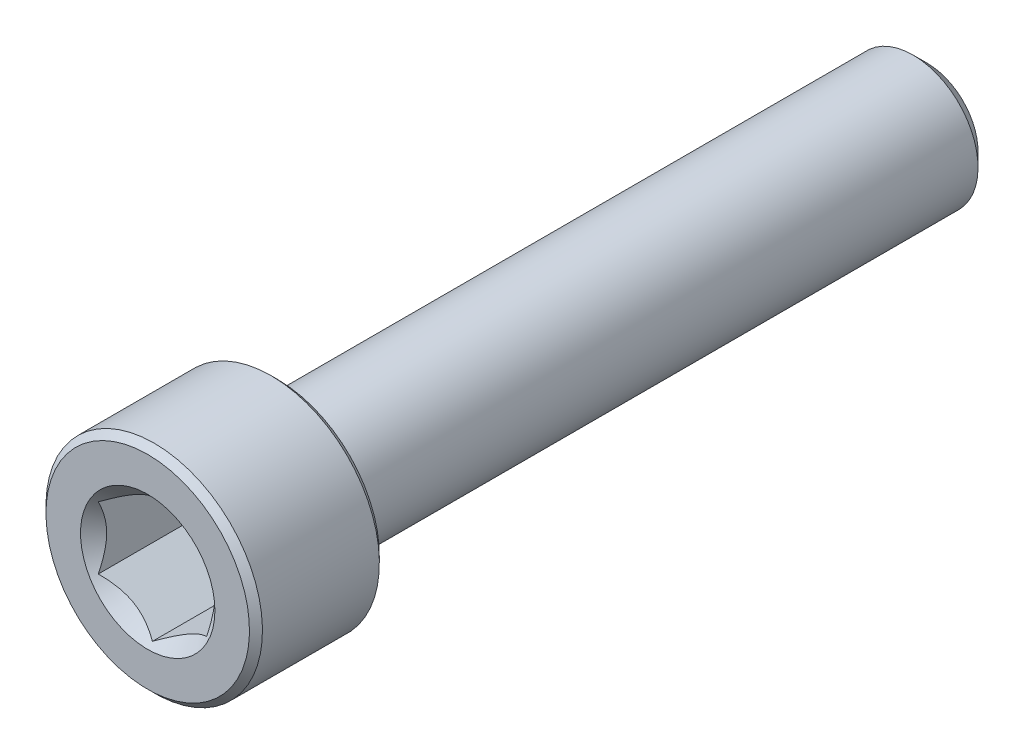
SolidWorks part; units mm, degrees
material "Alloy Steel"
ref_plane "Front Plane" through (0, 0, 0) normal (0, 0, 1) x (1, 0, 0)
ref_plane "Top Plane" through (0, 0, 0) normal (0, 1, 0) x (1, 0, 0)
ref_plane "Right Plane" through (0, 0, 0) normal (1, 0, 0) x (0, 0, -1)
sketch "Sketch1" plane through (0, 0, 0) normal (1, 0, 0) x (0, 0, -1)
  line L0 (-18, 0) -> (18, 0) construction
  line L1 (18, 0) -> (18, 2.3505) construction
  line L2 (18, 2.3505) -> (17.3505, 3) construction
  line L3 (17.3505, 3) -> (17.25, 3) construction
  line L4 (17.25, 3) -> (-12, 3) construction
  line L5 (-12, 3) -> (-12, 5) construction
  line L6 (-12, 5) -> (-18, 5) construction
  line L7 (-18, 5) -> (-18, 0) construction
  line L8 (18, 2.3505) -> (18, 3) construction
  line L9 (17.9375, 3.1083) -> (18.4375, 2.2422) construction
  line L10 (18.4375, 2.2422) -> (18.9375, 3.1083) construction
  line L11 (18.9375, 3.1083) -> (17.9375, 3.1083) construction
  line L12 (18.4375, 3.1083) -> (18.4375, 3) construction
  line L13 (18.4375, 2.2422) -> (18.4375, 2.3505) construction
  line L14 (18.375, 2.3505) -> (18.5, 2.3505) construction
  line L15 (18, 3) -> (18.875, 3) construction
  line L16 (17.9687, 3.0541) -> (18.9063, 3.0541) construction
  line L17 (18, 0) -> (18, -3) construction
  line L18 (-12.3, 5) -> (-12, 4.7) construction
  line L19 (-17.7, 5) -> (-18, 4.7) construction
  line L20 (-12, 3) -> (-12, 0) construction
  line L21 (-12, 1.5) -> (-2, 1.5) construction
  line L22 (-2, 1.5) -> (8, 1.5) construction
  line L23 (8, 1.5) -> (18, 1.5) construction
  line L24 (-2, 1.5) -> (-2, 3) construction
  line L25 (-2, 3) -> (-2, 5) construction
  line L26 (8, 1.5) -> (8, 5) construction
  point P0 (-18, 2.5)
  point P3 (15.5, 3)
  point P4 (0, 0)
  point P18 (8, 3)
  point P22 (18.4375, 2.3505)
  point P24 (17.25, 3)
  point P25 (18.4375, 3)
  point P28 (18.4375, 3.0541)
  point P29 (15.5, -3)
  point P30 (-2, 3)
  point P31 (-15, 5)
  point P37 (-13.05, 5)
  point P38 (-17.55, 5)
  point P45 (-2, 1.5)
  point P46 (8, 1.5)
  dimension "D2" = 0.125
  dimension "D7" = 0.3
  dimension "D8" = 0.3
  dimension "D9" = 0.3
  dimension "D10" = 0.15
  dimension "D11" = 0.75
  dimension "Drive Size" = 5
  dimension "Head Diameter" = 10
  dimension "Head Height" = 6
  dimension "Thread Pitch" = 1
  dimension "Thread Dia" = 6
  dimension "Length" = 30
  dimension "D12" = 0.75
  dimension "D4" = 2.5
  dimension "D3" = 45
sketch "Sketch2" plane through (0, 0, 0) normal (1, 0, 0) x (0, 0, -1)
  line L0 (-18, 0) -> (-18, 4.7)
  line L1 (-17.7, 5) -> (-12.3, 5)
  line L2 (-12, 4.7) -> (-12, 3.3)
  line L4 (17.3505, 3) -> (18, 2.3505)
  line L5 (18, 2.3505) -> (18, 0)
  line L6 (-12, 5) -> (-18, 5) construction
  line L7 (18, 0) -> (-18, 0)
  line L8 (-17.7, 5) -> (-18, 4.7) construction
  line L10 (-17.7, 5) -> (-18, 4.7)
  line L14 (-12.3, 5) -> (-12, 4.7) construction
  line L16 (-12.3, 5) -> (-12, 4.7)
  line L17 (-12, 3) -> (-12, 5) construction
  line L19 (-11.7, 3) -> (17.3505, 3)
  line L20 (17.25, 3) -> (-12, 3) construction
  arc A1 (-12, 3.3) -> (-11.7, 3) centre (-11.7, 3.3) ccw
  dimension "D3" = 0.3
revolve "Revolve1" add sketch "Sketch2" angle 360 about L7
sketch "Sketch3" plane through (0, 0, 18) normal (0, 0, 1) x (1, 0, 0)
  line L1 (2.5, -1.4434) -> (2.5, 1.4434)
  line L2 (2.5, 1.4434) -> (0, 2.8868)
  line L3 (0, 2.8868) -> (-2.5, 1.4434)
  line L4 (-2.5, 1.4434) -> (-2.5, -1.4434)
  line L5 (-2.5, -1.4434) -> (0, -2.8868)
  line L6 (0, -2.8868) -> (2.5, -1.4434)
  circle A0 centre (0, 0) radius 2.5 construction
  circle A1 centre (0, 0) radius 5 construction
  circle A2 centre (0, 0) radius 5 construction
  circle A3 centre (0, 0) radius 2.8868 construction
  point P13 (0, 0)
  dimension "D1" = 5.7735
extrude "Cut-Extrude1" cut sketch "Sketch3" against normal offset from surface (5 mm away) 1 up to face at (0, 4.7, 12)
sketch "Sketch4" plane through (0, 0, 18) normal (0, 0, 1) x (1, 0, 0)
  circle A0 centre (0, 0) radius 3.1033
  dimension "D1" = 6.2065
extrude "Cut-Extrude2" cut sketch "Sketch4" against normal up to vertex (3 mm away) draft 45 up to point (0, 5, 15)
sketch "Sketch11" plane through (0, 0, 0) normal (1, 0, 0) x (0, 0, -1)
  line L0 (-18, 0) -> (18, 0) construction
  line L1 (-18, 0) -> (18, 0) construction
  line L2 (-6.375, 0) -> (-6.375, 3) construction
  line L3 (17.25, 3) -> (-12, 3) construction
  line L4 (12.375, 0) -> (12.375, 3) construction
  line L6 (18, 2.3505) -> (18, 3) construction
  point P2 (-6.375, 0)
  point P3 (12.375, 0)
  dimension "D1" = 5.625
  dimension "D2" = 5.625
sketch "Sketch6" [suppressed] plane through (0, 0, -18) normal (0, 0, -1) x (-1, 0, 0)
  circle A0 centre (0, 0) radius 3
curve "Helix/Spiral1" [suppressed] pitch 1 height 31 turns 31
sketch "Sketch10" [suppressed] plane through (0, 0, 0) normal (1, 0, 0) x (0, 0, -1)
  line L0 (-11.7, -5) -> (-11.7, 5)
  line L5 (-18, 0) -> (18, 0) construction
  line L6 (-11.7, 3) -> (-11.7, -3) construction
  point P3 (-11.7, 0)
split "Split1" [suppressed] bodies to split 106
sketch "Sketch7" [suppressed] plane through (0, 0, 0) normal (1, 0, 0) x (0, 0, -1)
  line L0 (17.9687, 3.0541) -> (18.9063, 3.0541)
  line L1 (18.9063, 3.0541) -> (18.5, 2.3505)
  line L2 (18.5, 2.3505) -> (18.375, 2.3505)
  line L3 (18.375, 2.3505) -> (17.9687, 3.0541)
sweep "Cut-Sweep1" [suppressed] cut profiles "Sketch7" path "Helix/Spiral1"
sketch "Sketch8" [suppressed] plane through (0, 0, 0) normal (1, 0, 0) x (0, 0, -1)
  line L0 (-12, 0) -> (-12, 3)
  line L1 (-11.7, -3) -> (-11.7, 3) construction
  line L2 (-12, 3) -> (-11.7, 3)
  line L4 (-11.7, 3) -> (-9.9679, 0)
  line L5 (-9.9679, 0) -> (-12, 0)
  line L6 (17.25, 3) -> (-12, 3) construction
  line L7 (-18, 0) -> (18, 0) construction
  dimension "D1" = 60
revolve "Revolve2" [suppressed] add sketch "Sketch8" angle 360 about L5
equation "\"D2@Sketch1\" = \"Thread Pitch@Sketch1\" / 8"
equation "\"D4@Helix/Spiral1\" = \"Thread Pitch@Sketch1\""
equation "\"D7@Sketch1\" = \"Head Height@Sketch1\" * .05"
equation "\"D8@Sketch1\"=\"D7@Sketch1\""
equation "\"D9@Sketch1\"=\"D7@Sketch1\""
equation "\"D10@Sketch1\"=\"D7@Sketch1\"/2"
equation "\"D11@Sketch1\"=\"D10@Sketch1\"*5"
equation "\"D4@Sketch1\"=\"Thread Pitch@Sketch1\"*2.5"
equation "\"D12@Sketch1\"=\"Thread Pitch@Sketch1\"*.75"
equation "\"D3@Helix/Spiral1\"=\"Length@Sketch1\"+\"Thread Pitch@Sketch1\""
equation "\"D3@Sketch2\"=\"Thread Dia@Sketch1\"*0.05"
equation "\"D1@Sketch11\"=\"Length@Sketch1\"*0.1875"
equation "\"D2@Sketch11\"=\"D1@Sketch11\""
equation "\"D1@Sketch4\"=\"D1@Sketch3\"*1.075"
